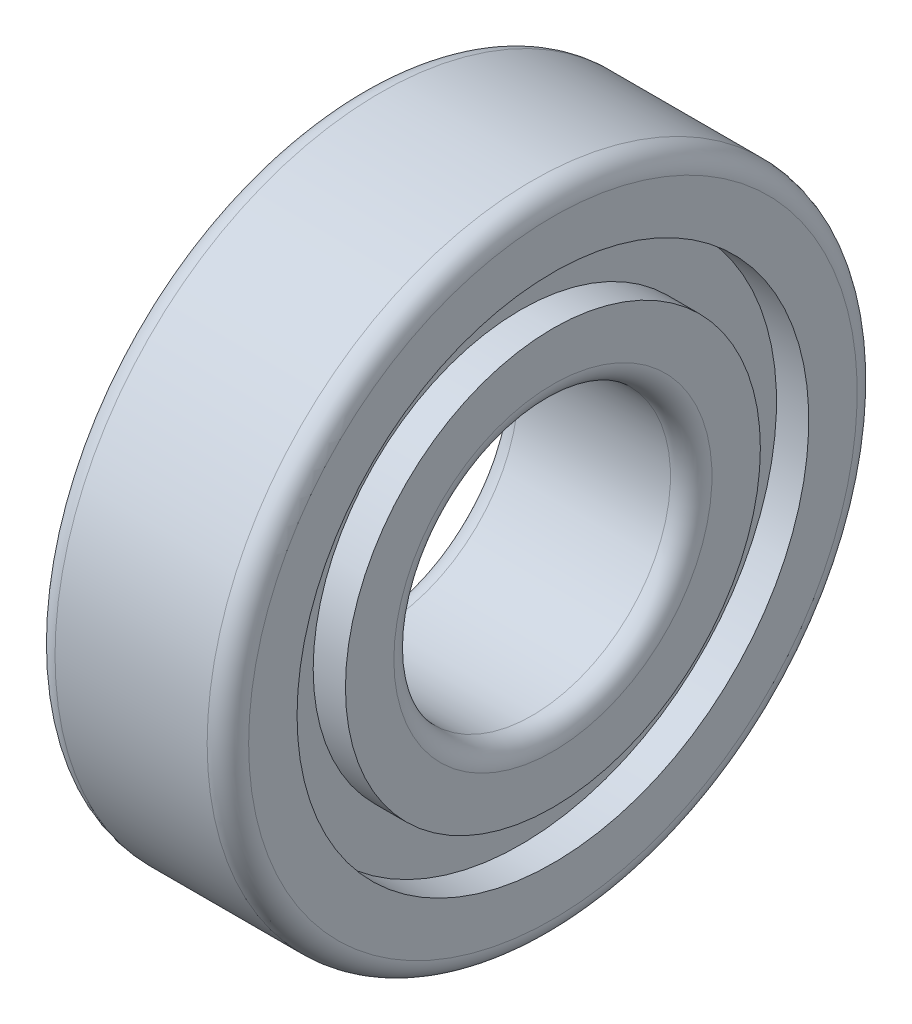
SolidWorks part; units mm, degrees
material "AISI 1020"
ref_plane "Спереди" through (0, 0, 0) normal (0, 0, 1) x (1, 0, 0)
ref_plane "Сверху" through (0, 0, 0) normal (0, 1, 0) x (1, 0, 0)
ref_plane "Справа" through (0, 0, 0) normal (1, 0, 0) x (0, 0, -1)
sketch "Эскиз1" plane through (0, 0, 0) normal (0, 0, 1) x (1, 0, 0)
  line L0 (-1000, 0) -> (49000, 0) construction
  line L1 (0, -1000) -> (0, 49000) construction
  line L2 (5.5, 10) -> (-5.5, 10)
  line L3 (-7, 11.5) -> (-7, 15)
  line L4 (-7, 15) -> (-4.6667, 15)
  line L5 (-4.6667, 15) -> (-4.6667, 18.5)
  line L6 (-4.6667, 18.5) -> (-7, 18.5)
  line L7 (-7, 18.5) -> (-7, 22)
  line L8 (-5.5, 23.5) -> (5.5, 23.5)
  line L9 (7, 18.5) -> (7, 22)
  line L10 (4.6667, 18.5) -> (7, 18.5)
  line L11 (4.6667, 15) -> (4.6667, 18.5)
  line L12 (7, 15) -> (4.6667, 15)
  line L13 (7, 11.5) -> (7, 15)
  arc A0 (-5.5, 10) -> (-7, 11.5) centre (-5.5, 11.5) cw
  arc A1 (-7, 22) -> (-5.5, 23.5) centre (-5.5, 22) cw
  arc A2 (7, 22) -> (5.5, 23.5) centre (5.5, 22) ccw
  arc A3 (5.5, 10) -> (7, 11.5) centre (5.5, 11.5) ccw
  point P23 (0, 23.5)
  point P27 (0, 10)
  dimension "_r" = 1.5
  dimension "_d" = 20
  dimension "D" = 47
  dimension "B" = 14
  dimension "D2" = 9.3333
revolve "Повернуть1" add sketch "Эскиз1" angle 360 about L0
equation "\"D2@Эскиз1\"= \"B@Эскиз1\" / 3 * 2"
